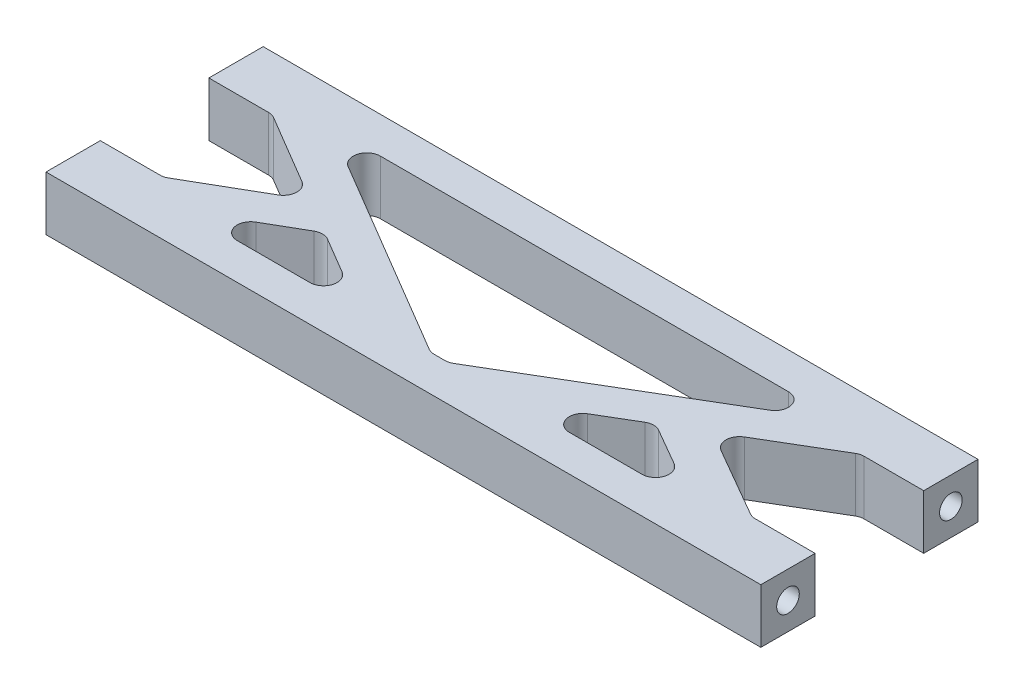
SolidWorks part; units mm, degrees
material "1060 Alloy"
ref_plane "Front Plane" through (0, 0, 0) normal (0, 0, 1) x (1, 0, 0)
ref_plane "Top Plane" through (0, 0, 0) normal (0, 1, 0) x (1, 0, 0)
ref_plane "Right Plane" through (0, 0, 0) normal (1, 0, 0) x (0, 0, -1)
sketch "Sketch1" plane through (0, 0, 0) normal (0, 1, 0) x (1, 0, 0)
  line L1 (0, 0) -> (79, 0)
  line L2 (0, 0) -> (0, 24)
  line L3 (0, 24) -> (79, 24)
  line L4 (79, 0) -> (79, 24)
  dimension "D1" = 24
  dimension "D2" = 79
extrude "Boss-Extrude1" add sketch "Sketch1" along normal blind 6
sketch "Sketch2" plane through (0, 6, 0) normal (0, 1, 0) x (1, 0, 0)
  line L0 (0, 18) -> (7, 18)
  line L2 (0, 24) -> (0, 0) construction
  line L3 (11.4736, 20) -> (67.5264, 20)
  line L4 (7, 6) -> (0, 6)
  line L6 (0, 6) -> (0, 18)
  line L7 (79, 18) -> (72, 18)
  line L8 (79, 0) -> (79, 24) construction
  line L9 (67.5264, 20) -> (40.5, 4)
  line L10 (72, 6) -> (79, 6)
  line L11 (79, 6) -> (79, 18)
  line L12 (40.5, 4) -> (38.5, 4)
  line L13 (38.5, 4) -> (11.4736, 20)
  line L14 (7, 18) -> (17.262, 11.9248)
  line L15 (17.262, 11.9248) -> (7, 6)
  line L16 (79, 24) -> (0, 24) construction
  line L17 (0, 0) -> (79, 0) construction
  line L18 (21.2118, 9.5864) -> (11.5359, 4)
  line L19 (11.5359, 4) -> (30.6481, 4)
  line L20 (30.6481, 4) -> (21.2118, 9.5864)
  line L21 (48.3519, 4) -> (57.7882, 9.5864)
  line L22 (57.7882, 9.5864) -> (67.4641, 4)
  line L23 (67.4641, 4) -> (48.3519, 4)
  line L24 (72, 6) -> (61.738, 11.9248)
  line L25 (61.738, 11.9248) -> (72, 18)
  dimension "D4" = 4
  dimension "D5" = 4
  dimension "D1" = 6
  dimension "D2" = 6
  dimension "D3" = 4
  dimension "D6" = 4
  dimension "D7" = 4
  dimension "D8" = 4
  dimension "D9" = 2
  dimension "D10" = 30
  dimension "D11" = 7
extrude "Cut-Extrude1" cut sketch "Sketch2" against normal up to next
hole_wizard "Tap Drill for M3 Tap1" positions "Sketch4" profile "Sketch3" hole size "M3" standard "ISO"
sketch "Sketch4" plane through (0, 0, 0) normal (-1, 0, 0) x (0, 0, 1)
  line L0 (-24, 0) -> (-18, 0) construction
  line L1 (-24, 6) -> (-24, 0) construction
  line L2 (0, 6) -> (0, 0) construction
  point P0 (-21, 3)
  point P2 (-3, 3)
  dimension "D1" = 3
  dimension "D2" = 3
  dimension "D3" = 3
sketch "Sketch3" plane through (0, 3, -21) normal (0, 1, 0) x (0, 0, 1)
  line L0 (0, 0) -> (0, 10.7511)
  line L1 (0, 10.7511) -> (1.25, 10)
  line L2 (1.25, 10) -> (1.25, 0)
  line L5 (1.25, 0) -> (0, 0)
  line L10 (0, 10.7511) -> (-1.25, 10) construction
  line L11 (0, -6.35) -> (0, 107.95) construction
  dimension "Hole Dia." = 2.5
  dimension "Hole Depth" = 10
  dimension "Drill Angle" = 118
hole_wizard "Tap Drill for M3 Tap2" positions "Sketch6" profile "Sketch5" hole size "M3" standard "ISO"
sketch "Sketch6" plane through (79, 0, 0) normal (1, 0, 0) x (0, 0, -1)
  line L0 (0, 0) -> (6, 0) construction
  line L1 (0, 6) -> (0, 0) construction
  line L2 (24, 6) -> (24, 0) construction
  point P0 (3, 3)
  point P2 (21, 3)
  dimension "D1" = 3
  dimension "D2" = 3
  dimension "D3" = 3
sketch "Sketch5" plane through (79, 3, -3) normal (0, 1, 0) x (0, 0, -1)
  line L0 (0, 0) -> (0, 10.7511)
  line L1 (0, 10.7511) -> (1.25, 10)
  line L2 (1.25, 10) -> (1.25, 0)
  line L5 (1.25, 0) -> (0, 0)
  line L10 (0, 10.7511) -> (-1.25, 10) construction
  line L11 (0, -6.35) -> (0, 107.95) construction
  dimension "Hole Dia." = 2.5
  dimension "Hole Depth" = 10
  dimension "Drill Angle" = 118
fillet "Fillet1" radius 1.5 16 edges at (48.3519, 3, -4) (57.7882, 3, -9.5864) (72, 3, -6) (61.738, 3, -11.9248) (72, 3, -18) (67.5264, 3, -20) (40.5, 3, -4) (38.5, 3, -4) (11.4736, 3, -20) (30.6481, 3, -4) (21.2118, 3, -9.5864) (7, 3, -6) (17.262, 3, -11.9248) (7, 3, -18) (67.4641, 3, -4) (11.5359, 3, -4)
